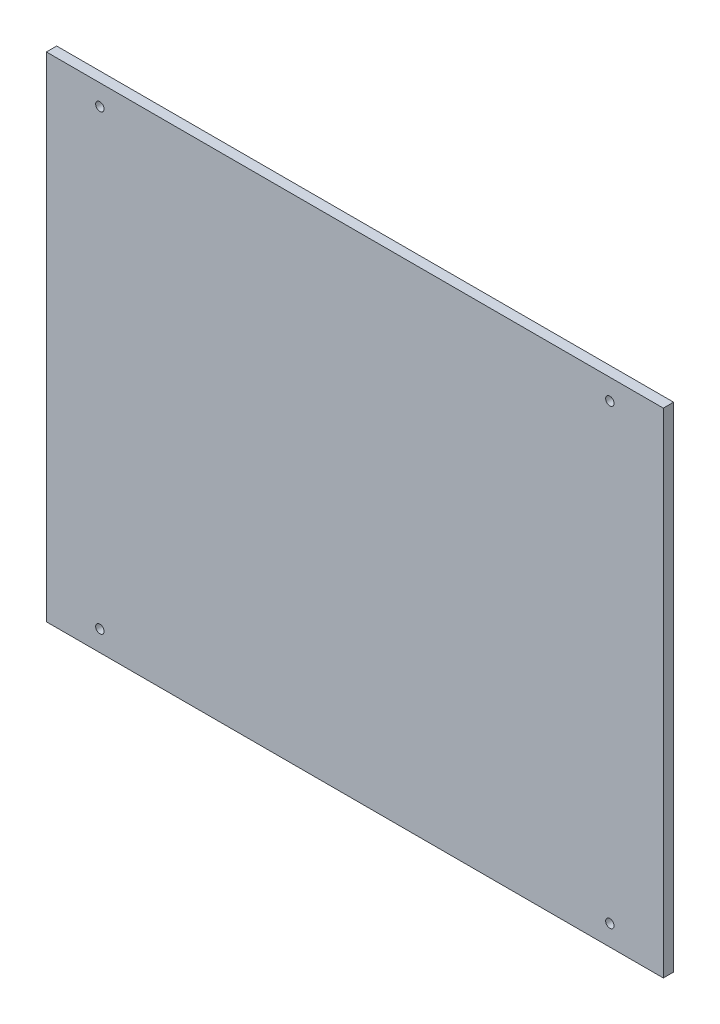
SolidWorks part; units mm, degrees
ref_plane "Plan de face" through (0, 0, 0) normal (0, 0, 1) x (1, 0, 0)
ref_plane "Plan de dessus" through (0, 0, 0) normal (0, 1, 0) x (1, 0, 0)
ref_plane "Plan de droite" through (0, 0, 0) normal (1, 0, 0) x (0, 0, -1)
sketch "Esquisse1" plane through (0, 0, 0) normal (0, 0, 1) x (1, 0, 0)
  line L0 (0, 143.6349) -> (0, -151.1597) construction
  line L1 (150, 120) -> (-150, 120) construction
  line L2 (150, 120) -> (150, -120) construction
  line L3 (150, -120) -> (-150, -120) construction
  line L4 (-150, 120) -> (-150, -120) construction
  line L5 (150, 120) -> (-150, -120) construction
  line L6 (150, -120) -> (-150, 120) construction
  line L7 (-305.4178, 0) -> (251.4164, 0) construction
  line L9 (150, -120) -> (-150, -120)
  line L10 (150, -120) -> (150, 120)
  line L11 (150, 120) -> (-150, 120)
  line L12 (-150, -120) -> (-150, 120)
  line L13 (150, -120) -> (-150, 120) construction
  line L14 (150, 120) -> (-150, -120) construction
  circle A0 centre (-124, 110) radius 2.05
  circle A1 centre (-124, -110) radius 2.05
  circle A2 centre (124, -110) radius 2.05
  circle A3 centre (124, 110) radius 2.05
  point P0 (0, 0)
  point P18 (0, 0)
  dimension "D2" = 4.1
  dimension "D1" = 240
  dimension "D3" = 300
  dimension "D4" = 124
  dimension "D5" = 10
  dimension "D6" = 240
  dimension "D7" = 300
extrude "Boss.-Extru.1" add sketch "Esquisse1" against normal blind 5
